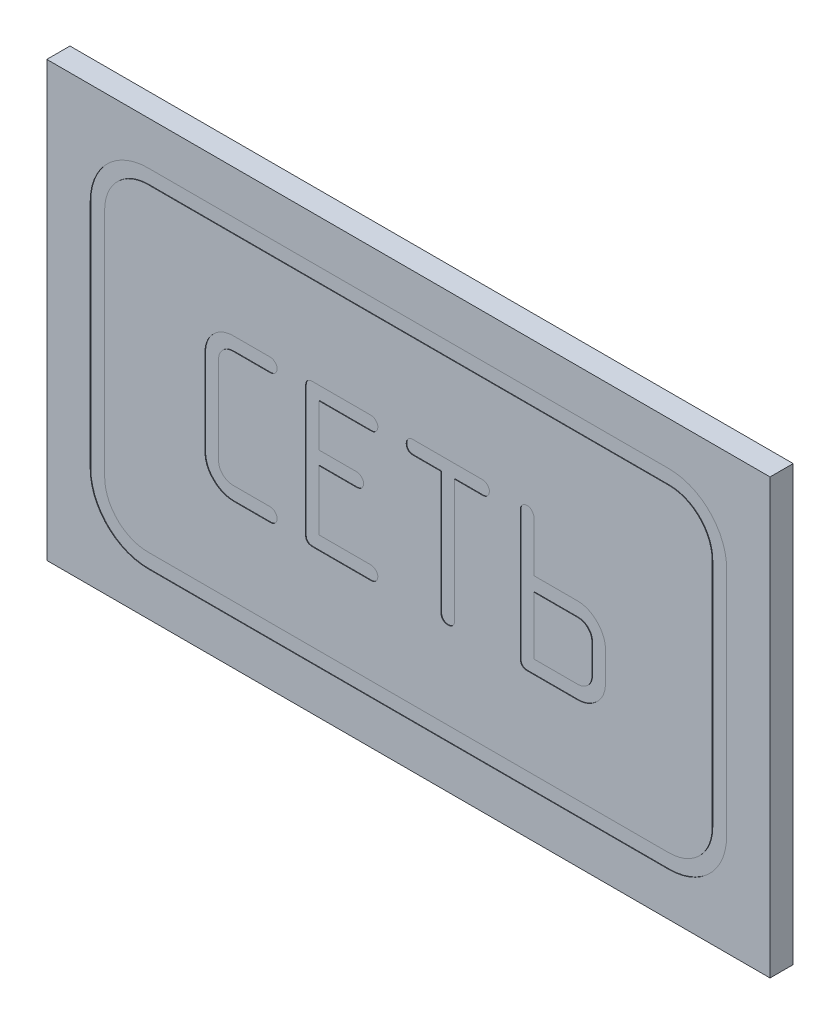
SolidWorks part; units mm, degrees
ref_plane "Спереди" through (0, 0, 0) normal (0, 0, 1) x (1, 0, 0)
ref_plane "Сверху" through (0, 0, 0) normal (0, 1, 0) x (1, 0, 0)
ref_plane "Справа" through (0, 0, 0) normal (1, 0, 0) x (0, 0, -1)
sketch "Эскиз1" plane through (0, 0, 0) normal (0, 0, 1) x (1, 0, 0)
  line L1 (0, 0) -> (25, 0)
  line L2 (0, 0) -> (0, 15)
  line L3 (0, 15) -> (25, 15)
  line L4 (25, 0) -> (25, 15)
  dimension "D1" = 15
  dimension "D2" = 25
extrude "Вытянуть1" add sketch "Эскиз1" along normal blind 0.8
sketch "Эскиз2" plane through (0, 0, 0.8) normal (0, 0, 1) x (1, 0, 0)
  line L0 (0, 0) -> (25, 0) construction
  line L1 (0, 15) -> (0, 0) construction
  text T0 "СЕТЬ" font "GOST type B" height 5
  dimension "D1" = 5
  dimension "D2" = 5
extrude "Вырез-Вытянуть1" cut sketch "Эскиз2" against normal blind 0.02
sketch "Эскиз3" plane through (0, 0, 0.8) normal (0, 0, 1) x (1, 0, 0)
  line L0 (25, 15) -> (0, 15) construction
  line L1 (3.5, 2) -> (21.5, 2)
  line L2 (2, 3.5) -> (2, 11.5)
  line L3 (3.5, 13) -> (21.5, 13)
  line L4 (23, 3.5) -> (23, 11.5)
  line L5 (0, 15) -> (0, 0) construction
  line L6 (0, 0) -> (25, 0) construction
  line L7 (25, 0) -> (25, 15) construction
  arc A0 (2, 11.5) -> (3.5, 13) centre (3.5, 11.5) cw
  arc A1 (21.5, 13) -> (23, 11.5) centre (21.5, 11.5) cw
  arc A2 (21.5, 2) -> (23, 3.5) centre (21.5, 3.5) ccw
  arc A3 (3.5, 2) -> (2, 3.5) centre (3.5, 3.5) cw
  dimension "D5" = 1.5
  dimension "D1" = 2
  dimension "D2" = 2
  dimension "D3" = 2
  dimension "D4" = 2
extrude "Вырез-Вытянуть-Тонкостенный1" cut sketch "Эскиз3" against normal blind 0.02 and the other way blind 0.02 thin thin type one direction wall 0.5
